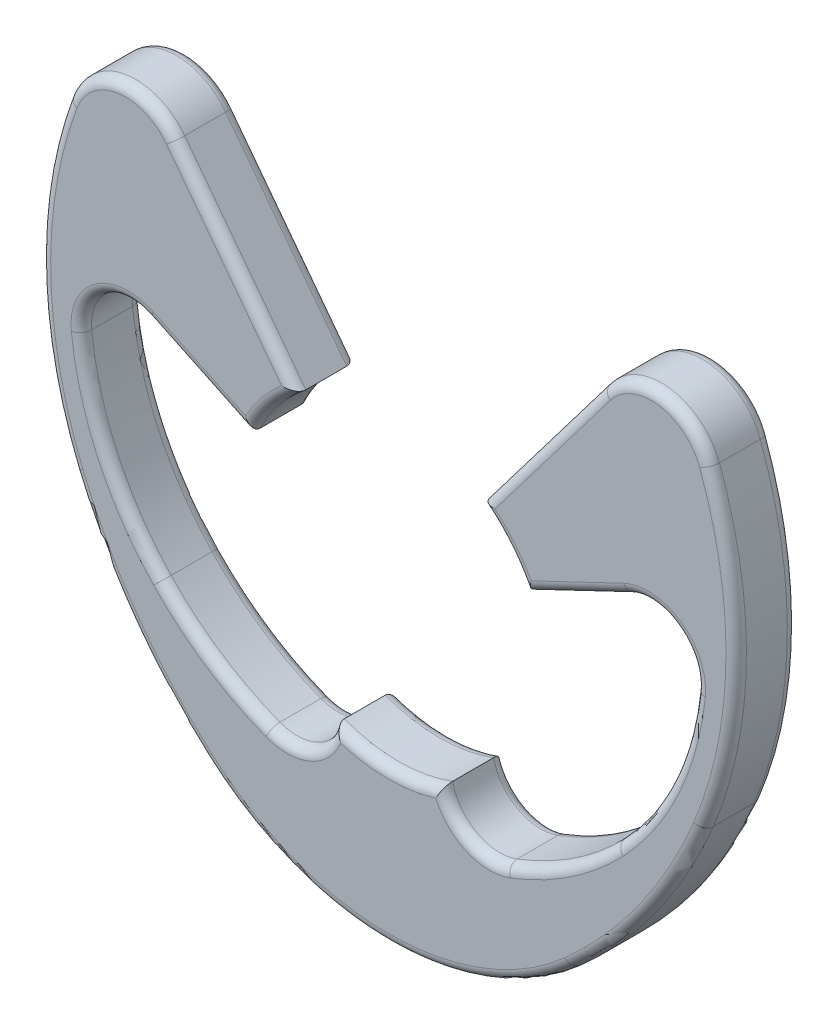
SolidWorks part; units mm, degrees
ref_plane "前视基准面" through (0, 0, 0) normal (0, 0, 1) x (1, 0, 0)
ref_plane "上视基准面" through (0, 0, 0) normal (0, 1, 0) x (1, 0, 0)
ref_plane "右视基准面" through (0, 0, 0) normal (1, 0, 0) x (0, 0, -1)
sketch "草图1" plane through (0, 0, 0) normal (0, 0, 1) x (1, 0, 0)
  line L0 (0, 0) -> (0, -1.5) construction
  line L1 (0.907, 1.1947) -> (2.0916, 2.7552)
  line L2 (1.3534, 0.6467) -> (2.3432, 1.1196)
  line L3 (-1.3534, 0.6467) -> (-2.3432, 1.1196)
  line L4 (-0.907, 1.1947) -> (-2.0916, 2.7552)
  arc A0 (-0.907, 1.1947) -> (-1.3534, 0.6467) centre (0, 0) ccw
  arc A1 (2.0916, 2.7552) -> (3.1391, 2.5992) centre (2.5726, 2.39) cw
  arc A2 (3.1391, 2.5992) -> (3.08, -0.5113) centre (-0.8685, 1.1196) cw
  arc A3 (3.08, -0.5113) -> (1.7939, -2.3244) centre (-1.5197, 1.3885) cw
  arc A4 (1.7939, -2.3244) -> (-1.7939, -2.3244) centre (0, -0.3143) cw
  arc A5 (2.3432, 1.1196) -> (3.0022, 0.6553) centre (2.5425, 0.7025) cw
  arc A6 (3.0022, 0.6553) -> (2.2247, -1.0362) centre (0.1317, 0.9503) cw
  arc A7 (2.2247, -1.0362) -> (1.16, -1.747) centre (0.1236, 0.9581) cw
  arc A8 (1.16, -1.747) -> (0.5298, -1.4033) centre (0.9913, -1.3067) cw
  arc A9 (-3.0022, 0.6553) -> (-2.2247, -1.0362) centre (-0.1317, 0.9503) ccw
  arc A10 (-3.08, -0.5113) -> (-1.7939, -2.3244) centre (1.5197, 1.3885) ccw
  arc A11 (-2.3432, 1.1196) -> (-3.0022, 0.6553) centre (-2.5425, 0.7025) ccw
  arc A12 (-3.1391, 2.5992) -> (-3.08, -0.5113) centre (0.8685, 1.1196) ccw
  arc A13 (-2.0916, 2.7552) -> (-3.1391, 2.5992) centre (-2.5726, 2.39) ccw
  arc A14 (-2.2247, -1.0362) -> (-1.16, -1.747) centre (-0.1236, 0.9581) ccw
  arc A15 (-1.16, -1.747) -> (-0.5298, -1.4033) centre (-0.9913, -1.3067) ccw
  arc A16 (1.3534, 0.6467) -> (0.907, 1.1947) centre (0, 0) ccw
  arc A17 (-0.5298, -1.4033) -> (0.5298, -1.4033) centre (0, 0) ccw
  dimension "D1" = 3
extrude "凸台-拉伸1" add sketch "草图1" along normal blind 0.6
fillet "圆角1" radius 0.1 44 edges at (1.8483, 0.8831, 0) (2.8087, 1.0804, 0) (2.7536, -0.2549, 0) (1.7321, -1.4511, 0) (0.7656, -1.7207, 0) (0, -1.5, 0) (-0.7656, -1.7207, 0) (-1.7321, -1.4511, 0) (-2.7536, -0.2549, 0) (-2.8087, 1.0804, 0) (-1.8483, 0.8831, 0) (-1.163, 0.9474, 0) (-1.4993, 1.9749, 0) (-2.6615, 2.9873, 0) (-3.4028, 1.0383, 0) (-2.5395, -1.4906, 0) (0, -3.0085, 0) (2.5395, -1.4906, 0) (3.4028, 1.0383, 0) (2.6615, 2.9873, 0) (1.4993, 1.9749, 0) (1.163, 0.9474, 0) (1.4993, 1.9749, 0.6) (2.6615, 2.9873, 0.6) (3.4028, 1.0383, 0.6) (2.5395, -1.4906, 0.6) (0, -3.0085, 0.6) (-2.5395, -1.4906, 0.6) (-3.4028, 1.0383, 0.6) (-2.6615, 2.9873, 0.6) (-1.4993, 1.9749, 0.6) (-1.163, 0.9474, 0.6) (-1.8483, 0.8831, 0.6) (-2.8087, 1.0804, 0.6) (-2.7536, -0.2549, 0.6) (-1.7321, -1.4511, 0.6) (-0.7656, -1.7207, 0.6) (0, -1.5, 0.6) (0.7656, -1.7207, 0.6) (1.7321, -1.4511, 0.6) (2.7536, -0.2549, 0.6) (2.8087, 1.0804, 0.6) (1.8483, 0.8831, 0.6) (1.163, 0.9474, 0.6)
